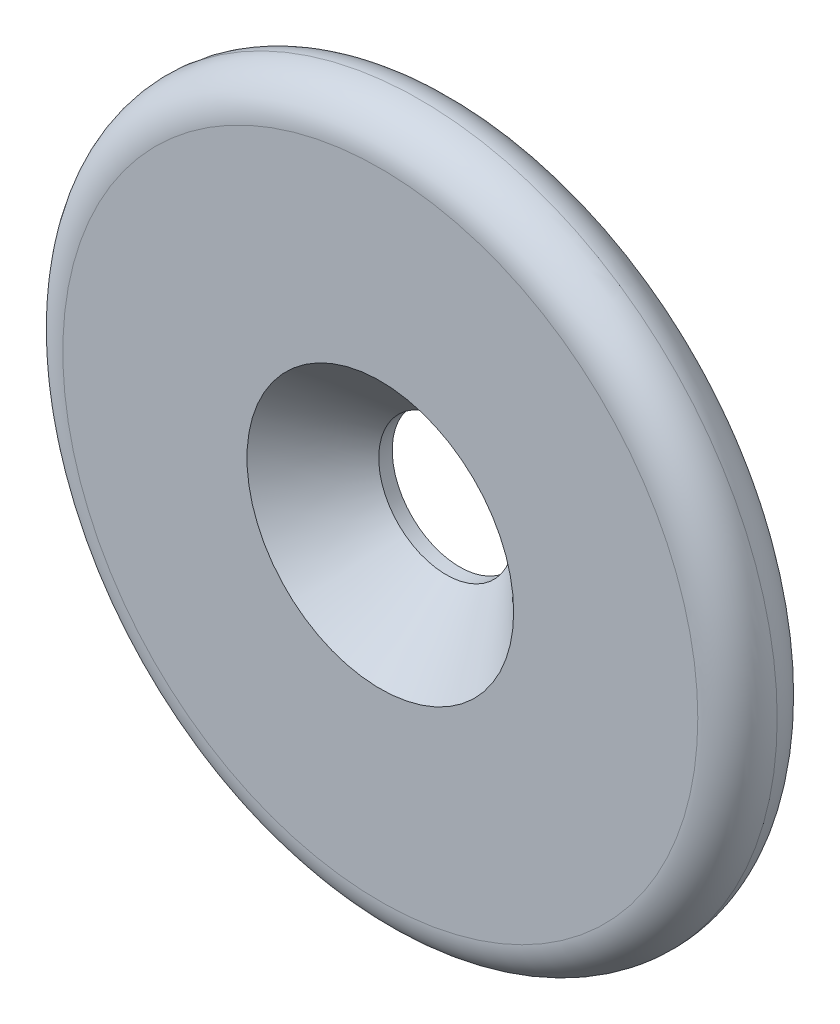
SolidWorks part; units mm, degrees
ref_plane "前视基准面" through (0, 0, 0) normal (0, 0, 1) x (1, 0, 0)
ref_plane "上视基准面" through (0, 0, 0) normal (0, 1, 0) x (1, 0, 0)
ref_plane "右视基准面" through (0, 0, 0) normal (1, 0, 0) x (0, 0, -1)
sketch "草图1" plane through (0, 0, 0) normal (0, 0, 1) x (1, 0, 0)
  circle A1 centre (0, 0) radius 9
  dimension "D1" = 18
extrude "凸台-拉伸1" add sketch "草图1" along normal blind 2
sketch "草图2" plane through (0, 0, 2) normal (0, 0, 1) x (1, 0, 0)
  point P0 (0, 0)
hole_wizard "M3 六角凹锥坑螺钉的锥形沉头孔1" positions "草图2" profile "草图3" countersink size "M3" standard "ISO" end condition through all
sketch "草图3" plane through (0, 0, 2) normal (1, 0, 0) x (0, -1, 0)
  line L0 (0, 0) -> (0, 2)
  line L1 (0, 2) -> (1.7, 2)
  line L2 (1.7, 2) -> (1.7, 1.66)
  line L3 (1.7, 1.66) -> (3.36, 0)
  line L5 (3.36, 0) -> (0, 0)
  line L6 (-1.7, 1.66) -> (-3.36, 0) construction
  line L11 (0, -6.35) -> (0, 107.95) construction
  dimension "通孔孔直径" = 3.4
  dimension "通孔孔深度" = 2
  dimension "近端锥形沉头孔直径" = 6.72
  dimension "近端锥形沉头孔角度" = 90
fillet "圆角1" radius 1 2 edges at (9, 0, 0) (9, 0, 2)
